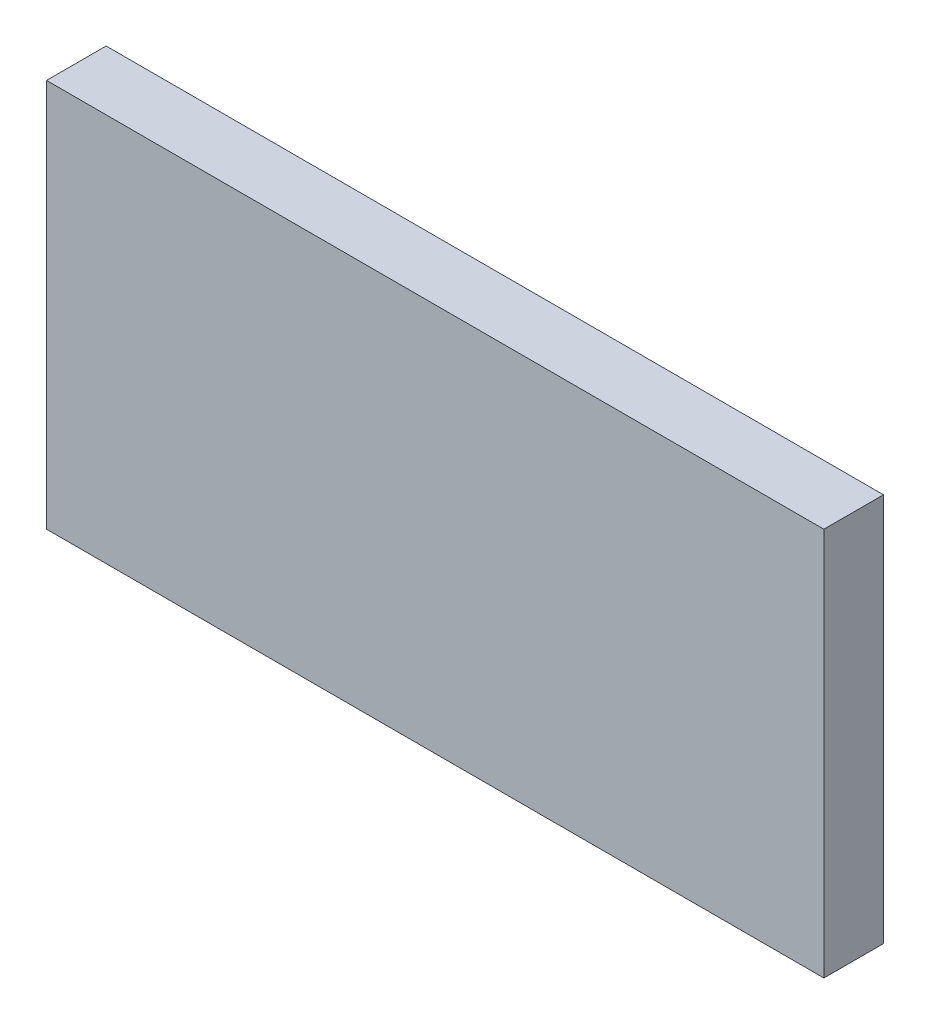
SolidWorks part; units mm, degrees
material "ABS PC"
ref_plane "Front Plane" through (0, 0, 0) normal (0, 0, 1) x (1, 0, 0)
ref_plane "Top Plane" through (0, 0, 0) normal (0, 1, 0) x (1, 0, 0)
ref_plane "Right Plane" through (0, 0, 0) normal (1, 0, 0) x (0, 0, -1)
sketch "Sketch1" plane through (0, 0, 0) normal (0, 0, 1) x (1, 0, 0)
  line L1 (0, 0) -> (38.1, 0)
  line L2 (0, 0) -> (0, 19.05)
  line L3 (0, 19.05) -> (38.1, 19.05)
  line L4 (38.1, 0) -> (38.1, 19.05)
  dimension "D1" = 19.05
  dimension "D2" = 38.1
extrude "Boss-Extrude1" add sketch "Sketch1" against normal blind 2.921
